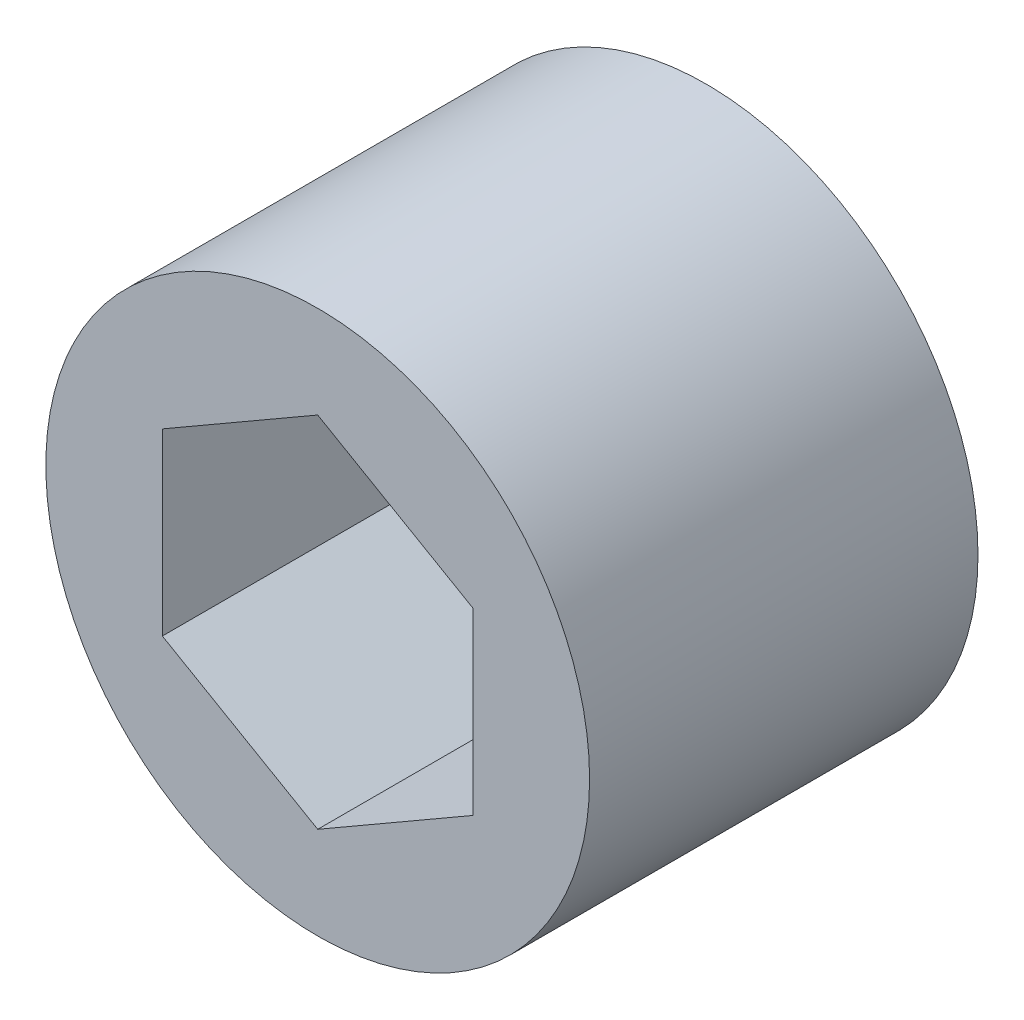
SolidWorks part; units mm, degrees
material "Nylon 101"
ref_plane "Front Plane" through (0, 0, 0) normal (0, 0, 1) x (1, 0, 0)
ref_plane "Top Plane" through (0, 0, 0) normal (0, 1, 0) x (1, 0, 0)
ref_plane "Right Plane" through (0, 0, 0) normal (1, 0, 0) x (0, 0, -1)
sketch "Sketch1" plane through (0, 0, 0) normal (0, 0, 1) x (1, 0, 0)
  line L1 (0, 7.3323) -> (-6.35, 3.6662)
  line L2 (-6.35, 3.6662) -> (-6.35, -3.6662)
  line L3 (-6.35, -3.6662) -> (0, -7.3323)
  line L4 (0, -7.3323) -> (6.35, -3.6662)
  line L5 (6.35, -3.6662) -> (6.35, 3.6662)
  line L6 (6.35, 3.6662) -> (0, 7.3323)
  circle A0 centre (0, 0) radius 6.35 construction
  circle A1 centre (0, 0) radius 11.1125
  dimension "D1" = 12.7
  dimension "D2" = 22.225
extrude "Boss-Extrude1" add sketch "Sketch1" along normal blind 15.875
sketch "Sketch2" plane through (0, 0, 0) normal (0, 0, -1) x (-1, 0, 0)
  line L0 (-6.6671, 4.2164) -> (-0.319, 7.8814) construction
  line L1 (-6.35, 3.6662) -> (0, 7.3323) construction
  text T0 "0019" font "Century Gothic" height in points 7
  point P4 (-6.6832, 4.207)
  point P5 (0, 0)
  point P6 (0, 0)
  point P7 (-6.6671, 4.2164)
  point P11 (0, 0)
  dimension "D1" = 0.635
extrude "Cut-Extrude1" cut sketch "Sketch2" against normal blind 0.4
